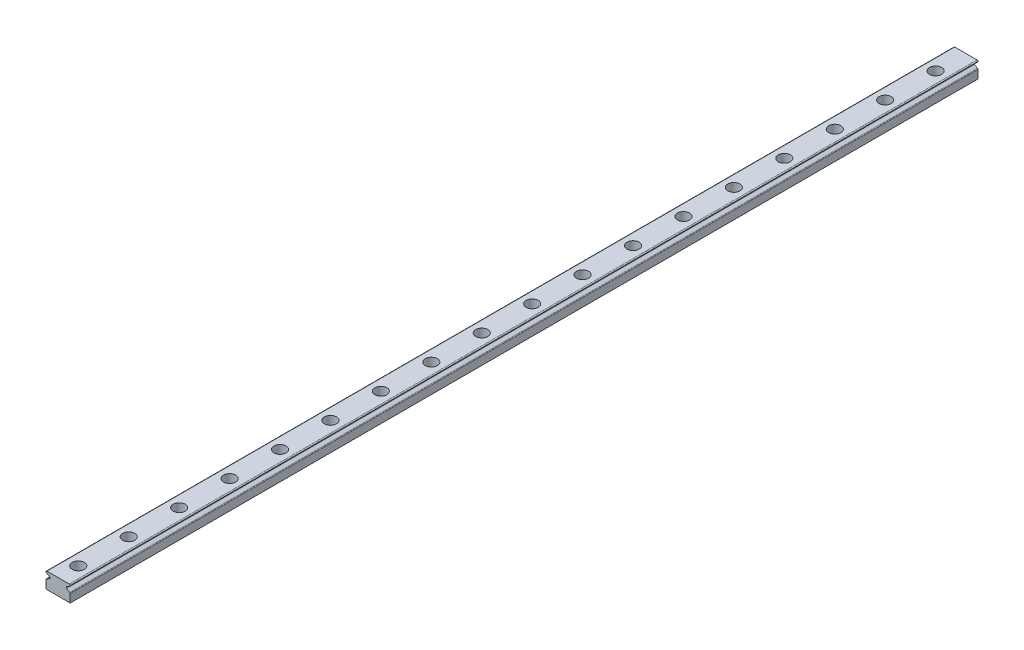
SolidWorks part; units mm, degrees
material "Plain Carbon Steel"
ref_plane "Front Plane" through (0, 0, 0) normal (0, 0, 1) x (1, 0, 0)
ref_plane "Top Plane" through (0, 0, 0) normal (0, 1, 0) x (1, 0, 0)
ref_plane "Right Plane" through (0, 0, 0) normal (1, 0, 0) x (0, 0, -1)
sketch "Sketch1" plane through (0, 0, 0) normal (0, 0, 1) x (1, 0, 0)
  line L4 (0, 0) -> (12, 0)
  line L5 (12, 0) -> (12, 8.4034)
  line L6 (12, 12) -> (0, 12)
  line L7 (0, 12) -> (0, 11.2902)
  line L8 (6, 12) -> (6, 7.6937) construction
  line L9 (6, 7.6937) -> (0, 7.6937) construction
  line L10 (0, 7.6937) -> (12, 7.6937) construction
  line L11 (6, 9.8468) -> (2.5, 9.8468) construction
  line L12 (6, 9.8468) -> (9.5, 9.8468) construction
  line L13 (9.5, 9.8468) -> (12, 11.2902)
  line L22 (9.5, 9.8468) -> (12, 8.4034)
  line L23 (2.5, 9.8468) -> (0, 11.2902)
  line L24 (2.5, 9.8468) -> (0, 8.4034)
  line L27 (12, 11.2902) -> (12, 12)
  line L28 (0, 8.4034) -> (0, 0)
  line L29 (7, 12) -> (7, 0) construction
  dimension "D3" = 3.5
  dimension "D1" = 6
  dimension "D2" = 7.6937
  dimension "D4" = 30
  dimension "D5" = 30
  dimension "D6" = 30
  dimension "D7" = 30
  dimension "D9" = 12
  dimension "D10" = 5
  dimension "D11" = 3.5
extrude "Boss-Extrude2" add sketch "Sketch1" along normal blind 450
fillet "Fillet5" radius 0.5 8 edges at (9.5, 9.8468, 225) (0, 12, 225) (12, 12, 225) (2.5, 9.8468, 225) (12, 8.4034, 225) (0, 8.4034, 225) (12, 11.2902, 225) (0, 11.2902, 225)
sketch "Sketch3" plane through (0, 12, 0) normal (0, 1, 0) x (1, 0, 0)
  line L0 (6, -450) -> (6, -490) construction
  line L1 (11.5, -450) -> (0.5, -450) construction
  line L2 (6, -490) -> (6, -440) construction
  line L3 (6, -440) -> (6, -465) construction
  circle A0 centre (6, -490) radius 3
  circle A1 centre (6, -440) radius 3
  circle A2 centre (6, -415) radius 3
  circle A3 centre (6, -390) radius 3
  circle A4 centre (6, -365) radius 3
  circle A5 centre (6, -340) radius 3
  circle A6 centre (6, -315) radius 3
  circle A7 centre (6, -290) radius 3
  circle A8 centre (6, -265) radius 3
  circle A9 centre (6, -240) radius 3
  circle A10 centre (6, -215) radius 3
  circle A11 centre (6, -190) radius 3
  circle A12 centre (6, -165) radius 3
  circle A13 centre (6, -140) radius 3
  circle A14 centre (6, -115) radius 3
  circle A15 centre (6, -90) radius 3
  circle A16 centre (6, -65) radius 3
  circle A17 centre (6, -40) radius 3
  circle A18 centre (6, -15) radius 3
  circle A19 centre (6, -465) radius 3
  dimension "D1" = 18
extrude "Cut-Extrude2" cut sketch "Sketch3" against normal blind 4.5
sketch "Sketch4" plane through (0, 12, 0) normal (0, 1, 0) x (1, 0, 0)
  line L0 (6, 0) -> (6, -15) construction
  line L1 (11.5, 0) -> (0.5, 0) construction
  circle A0 centre (6, -15) radius 1.75
  circle A1 centre (6, -40) radius 1.75
  circle A2 centre (6, -65) radius 1.75
  circle A3 centre (6, -90) radius 1.75
  circle A4 centre (6, -115) radius 1.75
  circle A5 centre (6, -140) radius 1.75
  circle A6 centre (6, -165) radius 1.75
  circle A7 centre (6, -190) radius 1.75
  circle A8 centre (6, -215) radius 1.75
  circle A9 centre (6, -240) radius 1.75
  circle A10 centre (6, -265) radius 1.75
  circle A11 centre (6, -290) radius 1.75
  circle A12 centre (6, -315) radius 1.75
  circle A13 centre (6, -340) radius 1.75
  circle A14 centre (6, -365) radius 1.75
  circle A15 centre (6, -390) radius 1.75
  circle A16 centre (6, -415) radius 1.75
  circle A17 centre (6, -440) radius 1.75
  circle A18 centre (6, -465) radius 1.75
  circle A19 centre (6, -490) radius 1.75
  dimension "D1" = 20
extrude "Cut-Extrude3" cut sketch "Sketch4" against normal blind 14.5
sketch "Sketch5" plane through (0, 0, 0) normal (0, 0, -1) x (-1, 0, 0)
  line L0 (-12, 0) -> (-12, 4.0574)
  line L2 (-12, 0) -> (-12, 8.1148) construction
  line L3 (-12, 4.0574) -> (0, 4.0574)
  line L4 (0, 8.1148) -> (0, 0) construction
  line L5 (0, 4.0574) -> (0, 0)
  line L6 (0, 0) -> (-12, 0)
extrude "Cut-Extrude4" cut sketch "Sketch5" against normal blind 682.5
